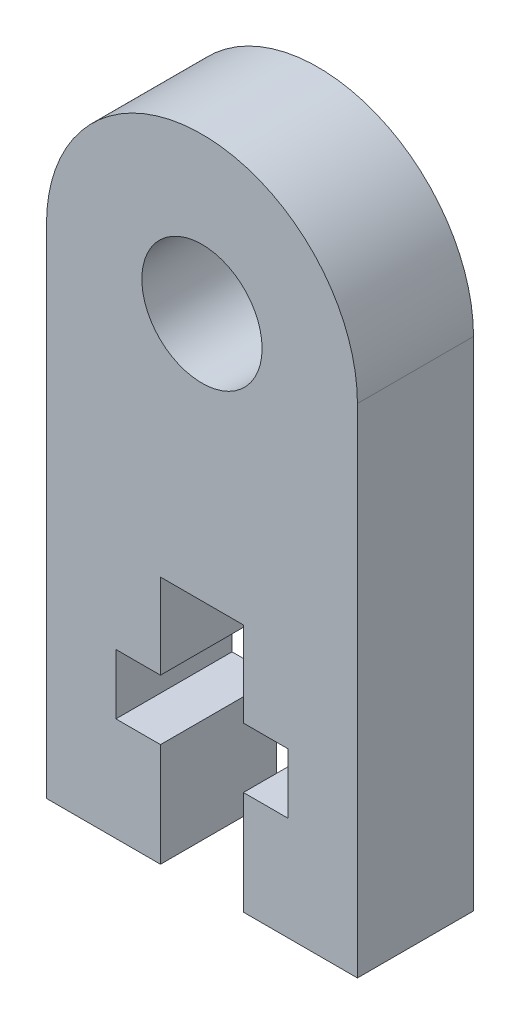
SolidWorks part; units mm, degrees
ref_plane "Front Plane" through (0, 0, 0) normal (0, 0, 1) x (1, 0, 0)
ref_plane "Top Plane" through (0, 0, 0) normal (0, 1, 0) x (1, 0, 0)
ref_plane "Right Plane" through (0, 0, 0) normal (1, 0, 0) x (0, 0, -1)
sketch "Sketch1" plane through (0, 0, 0) normal (0, 0, 1) x (1, 0, 0)
  line L0 (0, 0) -> (-2.0506, 2.0506) construction
  line L1 (0, 0) -> (0, 2.9) construction
  line L2 (-7.5, 0) -> (-7.5, -24)
  line L3 (-7.5, -24) -> (7.5, -24)
  line L4 (7.5, -24) -> (7.5, 0)
  line L5 (0, 0) -> (0, -24) construction
  circle A0 centre (0, 0) radius 2.9
  arc A1 (-7.5, 0) -> (7.5, 0) centre (0, 0) cw
  dimension "D1" = 5.8
  dimension "D4" = 45
  dimension "D5" = 24
  dimension "D6" = 15
extrude "Boss-Extrude1" add sketch "Sketch1" along normal blind 5.6
sketch "Sketch3" plane through (0, 0, 5.6) normal (0, 0, 1) x (1, 0, 0)
  line L0 (-7.5, -24) -> (7.5, -24) construction
  line L1 (-2, -24) -> (2, -24)
  line L2 (-2, -24) -> (-2, -19)
  line L3 (-2, -12) -> (2, -12)
  line L4 (2, -24) -> (2, -19)
  line L5 (0, -12) -> (0, 0) construction
  line L6 (2, -16.1) -> (4.15, -16.1)
  line L7 (-4.15, -16.1) -> (-2, -16.1)
  line L8 (-4.15, -16.1) -> (-4.15, -19)
  line L9 (-4.15, -19) -> (-2, -19)
  line L10 (4.15, -16.1) -> (4.15, -19)
  line L11 (-2, -16.1) -> (-2, -12)
  line L12 (2, -19) -> (4.15, -19)
  line L13 (2, -16.1) -> (2, -12)
  point P18 (-3.075, -19)
  dimension "D1" = 4
  dimension "D3" = 12
  dimension "D4" = 8.3
  dimension "D5" = 2.9
  dimension "D6" = 5
extrude "Cut-Extrude2" cut sketch "Sketch3" against normal through all
equation "\"smallPulleyTeeth\"= 15"
equation "\"largePulleyTeeth\"= 30"
equation "\"eighthThick\"= 2.9mm"
equation "\"sixteenthThick\" = 1.7mm"
equation "\"quarterThick\"=5.6mm"
equation "\"OD\" = 150mm"
equation "\"puckAngle\" = 60.5deg"
equation "\"puckDiam\" = 76.5mm"
equation "\"axlePress\" = 5.8mm"
equation "\"D1@Sketch1\"=\"axlePress\""
equation "\"D1@Boss-Extrude1\"=\"quarterThick\""
equation "\"press\" = 0.3mm"
equation "\"wheelClear\" = 0.3mm"
equation "\"10-32clear\" = 4.5mm"
equation "\"D1@Sketch3\"=\"8-32clear\""
equation "\"6-32clear\" = 3.3mm"
equation "\"8-32clear\" = 4.0mm"
